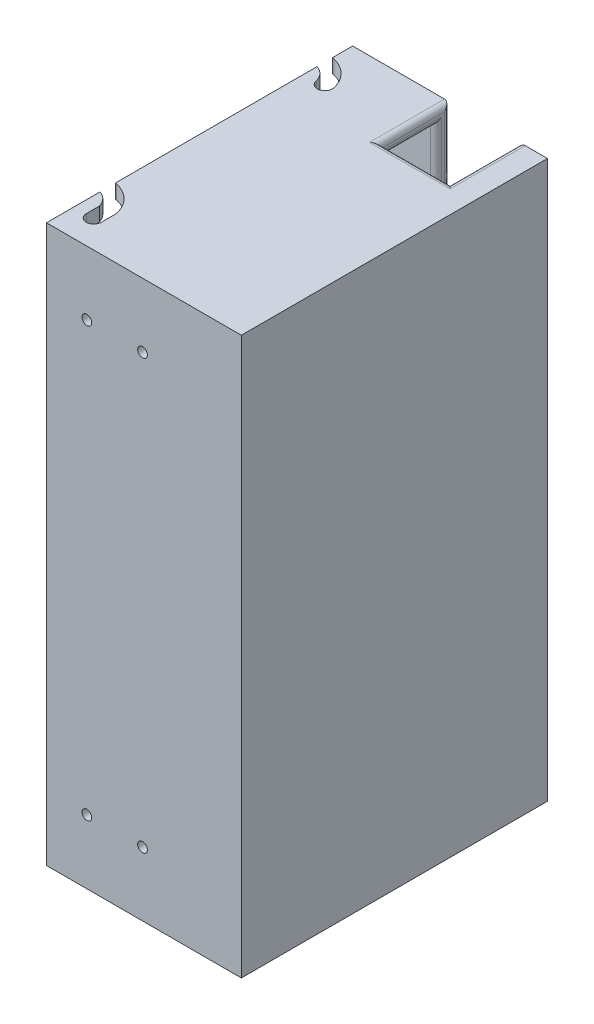
SolidWorks part; units mm, degrees
ref_plane "Plan de face" through (0, 0, 0) normal (0, 0, 1) x (1, 0, 0)
ref_plane "Plan de dessus" through (0, 0, 0) normal (0, 1, 0) x (1, 0, 0)
ref_plane "Plan de droite" through (0, 0, 0) normal (1, 0, 0) x (0, 0, -1)
sketch "Esquisse1" plane through (0, 0, 0) normal (0, 0, 1) x (1, 0, 0)
  line L9 (0, 0) -> (-70, 0)
  line L10 (0, 0) -> (0, 200)
  line L11 (0, 200) -> (-70, 200)
  line L12 (-70, 0) -> (-70, 200)
  dimension "D1" = 70
  dimension "D2" = 200
extrude "Boss.-Extru.1" add sketch "Esquisse1" along normal blind 5
sketch "Esquisse2" plane through (0, 0, 5) normal (0, 0, 1) x (1, 0, 0)
  line L0 (-70, 200) -> (-70, 0) construction
  line L1 (0, 0) -> (-70, 0)
  line L2 (0, 0) -> (0, 200)
  line L3 (0, 200) -> (-70, 200)
  line L5 (-5, 5) -> (-70, 5)
  line L6 (-5, 5) -> (-5, 195)
  line L7 (-5, 195) -> (-70, 195)
  line L9 (-70, 195) -> (-70, 200)
  line L10 (-70, 5) -> (-70, 0)
  dimension "D1" = 5
  dimension "D2" = 5
  dimension "D4" = 5
extrude "Boss.-Extru.2" add sketch "Esquisse2" along normal blind 100
sketch "Esquisse3" plane through (0, 0, 105) normal (0, 0, 1) x (1, 0, 0)
  line L1 (-70, 200) -> (0, 200)
  line L2 (-70, 200) -> (-70, 0)
  line L3 (-70, 0) -> (0, 0)
  line L4 (0, 200) -> (0, 0)
extrude "Boss.-Extru.3" add sketch "Esquisse3" along normal blind 5
sketch "Esquisse5" plane through (0, 0, 0) normal (0, -1, 0) x (1, 0, 0)
  line L0 (-70, 110) -> (-70, 0) construction
  line L4 (-70, 0) -> (-32, 0) construction
  line L7 (-63, 95) -> (-63, 100) construction
  line L13 (-65.7, 95) -> (-65.7, 100)
  line L14 (-60.3, 95) -> (-60.3, 100)
  arc A36 (-70, 10) -> (-63, 17) centre (-71.9836, 18.9836) ccw construction
  arc A37 (-69.4179, 7.3635) -> (-60.3635, 16.4179) centre (-71.9836, 18.9836) ccw
  arc A38 (-70.5821, 12.6365) -> (-65.6365, 17.5821) centre (-71.9836, 18.9836) ccw
  arc A39 (-70.5821, 12.6365) -> (-69.4179, 7.3635) centre (-70, 10) ccw
  arc A40 (-60.3635, 16.4179) -> (-65.6365, 17.5821) centre (-63, 17) ccw
  arc A41 (-70, 88) -> (-63, 95) centre (-71.9836, 96.9836) ccw construction
  arc A42 (-69.4179, 85.3635) -> (-60.3635, 94.4179) centre (-71.9836, 96.9836) ccw
  arc A43 (-70.5821, 90.6365) -> (-65.6365, 95.5821) centre (-71.9836, 96.9836) ccw
  arc A44 (-70.5821, 90.6365) -> (-69.4179, 85.3635) centre (-70, 88) ccw
  arc A45 (-60.3635, 94.4179) -> (-65.6365, 95.5821) centre (-63, 95) ccw
  arc A46 (-65.7, 95) -> (-60.3, 95) centre (-63, 95) ccw
  arc A47 (-60.3, 100) -> (-65.7, 100) centre (-63, 100) ccw
  point P3 (-65.4782, 12.4782)
  point P15 (-65.4782, 90.4782)
  point P22 (-63, 97.5)
  line M9 (-70, 110) -> (-70, 0)
  dimension "D1" = 2.7
  dimension "D2" = 7
  dimension "D5" = 2.7
  dimension "D3" = 10
  dimension "D4" = 6.5
  dimension "D7" = 7
  dimension "D12" = 7
  dimension "D11" = 7
  dimension "D6" = 6.5
  dimension "D8" = 2.7
  dimension "D9" = 5
  dimension "D10" = 83
extrude "Enlèv. mat.-Extru.2" cut sketch "Esquisse5" against normal blind 5 contours A37 A40 A38 A39 M9 | A46 L13 A43 A44 A42 M9 | L13 A46 A45 A43 | L14 A47 L13 A43 A45
ref_plane "Plan1" through (0, 100, 0) normal (0, 1, 0) x (1, 0, 0)
mirror "Symétrie1" about plane through (0, 100, 0) normal (0, 1, 0) of "Enlèv. mat.-Extru.2"
fillet "Congé3" radius 1 4 edges at (-70, 2.5, 90.7937) (-70, 2.5, 85.3) (-70, 2.5, 12.7937) (-70, 2.5, 7.3)
sketch "Esquisse7" plane through (0, 0, 110) normal (0, 0, 1) x (1, 0, 0)
  line L0 (-55.5, 23) -> (-35.5, 23) construction
  line L2 (-70, 100) -> (0, 100) construction
  line L3 (-70, 200) -> (-70, 0) construction
  line L4 (0, 0) -> (0, 200) construction
  circle A1 centre (-55.5, 23) radius 1.75
  circle A2 centre (-35.5, 23) radius 1.75
  circle A4 centre (-55.5, 177) radius 1.75
  circle A5 centre (-35.5, 177) radius 1.75
  dimension "D3" = 77
  dimension "D4" = 3.5
  dimension "D1" = 20
  dimension "D2" = 14.5
extrude "Enlèv. mat.-Extru.4" cut sketch "Esquisse7" against normal blind 5
sketch "Esquisse8" plane through (0, 0, 105) normal (0, 0, -1) x (-1, 0, 0)
  line L0 (0, 100) -> (70, 100) construction
  line L1 (0, 0) -> (0, 200) construction
  line L2 (70, 195) -> (70, 5) construction
  line L3 (33.8546, 25.85) -> (37.1454, 25.85)
  line L4 (37.1454, 25.85) -> (38.7909, 23)
  line L5 (38.7909, 23) -> (37.1454, 20.15)
  line L6 (37.1454, 20.15) -> (33.8546, 20.15)
  line L7 (33.8546, 20.15) -> (32.2091, 23)
  line L8 (32.2091, 23) -> (33.8546, 25.85)
  line L9 (32.2091, 23) -> (38.7909, 23) construction
  line L10 (53.8546, 25.85) -> (57.1454, 25.85)
  line L11 (57.1454, 25.85) -> (58.7909, 23)
  line L12 (58.7909, 23) -> (57.1454, 20.15)
  line L13 (57.1454, 20.15) -> (53.8546, 20.15)
  line L14 (53.8546, 20.15) -> (52.2091, 23)
  line L15 (52.2091, 23) -> (53.8546, 25.85)
  line L16 (52.2091, 23) -> (58.7909, 23) construction
  line L17 (52.2091, 177) -> (58.7909, 177) construction
  line L18 (32.2091, 177) -> (38.7909, 177) construction
  line L19 (52.2091, 177) -> (53.8546, 174.15)
  line L20 (53.8546, 179.85) -> (52.2091, 177)
  line L21 (57.1454, 179.85) -> (53.8546, 179.85)
  line L22 (58.7909, 177) -> (57.1454, 179.85)
  line L23 (57.1454, 174.15) -> (58.7909, 177)
  line L24 (53.8546, 174.15) -> (57.1454, 174.15)
  line L25 (32.2091, 177) -> (33.8546, 174.15)
  line L26 (33.8546, 179.85) -> (32.2091, 177)
  line L27 (37.1454, 179.85) -> (33.8546, 179.85)
  line L28 (38.7909, 177) -> (37.1454, 179.85)
  line L29 (37.1454, 174.15) -> (38.7909, 177)
  line L30 (33.8546, 174.15) -> (37.1454, 174.15)
  point P0 (55.5, 23)
  point P1 (35.5, 23)
  point P12 (35.5, 23)
  point P17 (35.5, 23)
  point P20 (55.5, 23)
  point P25 (55.5, 23)
  point P40 (55.5, 177)
  point P41 (35.5, 177)
  dimension "D1" = 120
  dimension "D2" = 5.7
  dimension "D3" = 120
  dimension "D4" = 5.7
extrude "Enlèv. mat.-Extru.5" cut sketch "Esquisse8" against normal blind 2
sketch "Esquisse9" plane through (0, 0, 0) normal (0, 0, -1) x (-1, 0, 0)
  line L0 (0, 0) -> (0, 200) construction
  line L1 (10, 200) -> (35, 200)
  line L2 (10, 200) -> (10, 175)
  line L3 (10, 175) -> (35, 175)
  line L4 (35, 200) -> (35, 175)
  line L6 (0, 200) -> (70, 200) construction
  dimension "D1" = 25
  dimension "D2" = 25
  dimension "D3" = 10
extrude "Enlèv. mat.-Extru.6" cut sketch "Esquisse9" against normal blind 25
fillet "Congé4" radius 2 12 edges at (-35, 185, 5) (-22.5, 175, 5) (-10, 185, 5) (-10, 195, 15) (-22.5, 200, 25) (-22.5, 195, 25) (-35, 200, 12.5) (-35, 195, 15) (-10, 200, 12.5) (-10, 187.5, 0) (-35, 187.5, 0) (-22.5, 175, 0)
